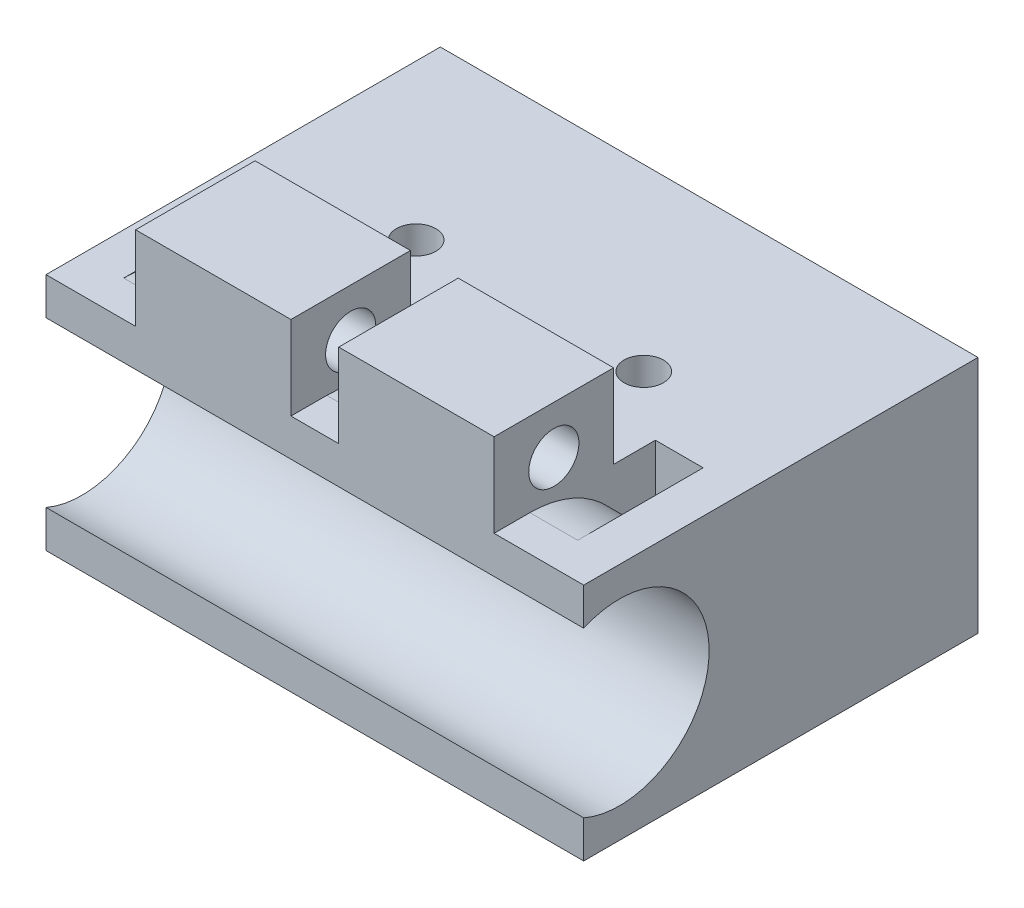
SolidWorks part; units mm, degrees
ref_plane "Front Plane" through (0, 0, 0) normal (0, 0, 1) x (1, 0, 0)
ref_plane "Top Plane" through (0, 0, 0) normal (0, 1, 0) x (1, 0, 0)
ref_plane "Right Plane" through (0, 0, 0) normal (1, 0, 0) x (0, 0, -1)
sketch "Sketch2" plane through (0, 0, 0) normal (0, 0, 1) x (1, 0, 0)
  line L1 (22.5, 10) -> (-22.5, 10)
  line L2 (22.5, 10) -> (22.5, -10)
  line L3 (22.5, -10) -> (-22.5, -10)
  line L4 (-22.5, 10) -> (-22.5, -10)
  line L5 (22.5, 10) -> (-22.5, -10) construction
  line L6 (22.5, -10) -> (-22.5, 10) construction
  point P0 (0, 0)
  dimension "D1" = 20
  dimension "D2" = 45
extrude "Boss-Extrude1" add sketch "Sketch2" along normal blind 33
sketch "Sketch3" plane through (22.5, 0, 0) normal (1, 0, 0) x (0, 0, -1)
  line L0 (-30, 0) -> (0, 0) construction
  circle A0 centre (-30, 0) radius 7.5
  dimension "D1" = 15
  dimension "D2" = 30
extrude "Cut-Extrude1" cut sketch "Sketch3" against normal blind 45
sketch "Sketch4" plane through (0, 0, 0) normal (0, 0, -1) x (-1, 0, 0)
  line L4 (22.5, -10) -> (22.5, 10)
  line L5 (22.5, 10) -> (-22.5, 10)
  line L6 (-22.5, 10) -> (-22.5, -10)
  line L7 (-22.5, -10) -> (22.5, -10)
  line L8 (22.5, -10) -> (22.5, 10)
  line L9 (22.5, 10) -> (-22.5, 10)
  line L10 (-22.5, 10) -> (-22.5, -10)
  line L11 (-22.5, -10) -> (22.5, -10)
  circle A0 centre (-15, 0) radius 4
  circle A1 centre (15, 0) radius 4
  dimension "D2" = 8
  dimension "D3" = 30
  dimension "D4" = 15
  dimension "D1" = 0
extrude "Cut-Extrude2" cut sketch "Sketch4" against normal blind 10 contours A0 | A1 region at (15, 0, 0) region at (-15, 0, 0)
sketch "Sketch5" plane through (0, -10, 0) normal (0, -1, 0) x (1, 0, 0)
  line L0 (0, 19.5) -> (0, 0) construction
  line L1 (-19, 21) -> (-15, 21)
  line L2 (-19, 21) -> (-19, 19.5)
  line L3 (-19, 19.5) -> (-15, 19.5)
  line L4 (-15, 21) -> (-15, 19.5)
  line L5 (-2, 19.5) -> (2, 19.5)
  line L6 (-2, 19.5) -> (-2, 21)
  line L7 (-2, 21) -> (2, 21)
  line L8 (2, 19.5) -> (2, 21)
  line L9 (15, 19.5) -> (19, 19.5)
  line L10 (15, 19.5) -> (15, 21)
  line L11 (15, 21) -> (19, 21)
  line L12 (19, 19.5) -> (19, 21)
  line L13 (-22.5, 19.5) -> (-19, 19.5) construction
  line L14 (-22.5, 33) -> (-22.5, 0) construction
  line L15 (-2, 19.5) -> (-15, 19.5) construction
  line L16 (2, 19.5) -> (15, 19.5) construction
  line L17 (19, 19.5) -> (22.5, 19.5) construction
  line L18 (22.5, 33) -> (22.5, 0) construction
  line L27 (-22.5, 0) -> (22.5, 0) construction
  dimension "D1" = 4
  dimension "D2" = 1.5
  dimension "D3" = 30
  dimension "D4" = 21
extrude "Cut-Extrude3" cut sketch "Sketch5" against normal blind 39
fillet "Fillet1" radius 9 3 edges at (17, -10, 21) (0, -10, 21) (-17, -10, 21)
hole_wizard "M4x0.7 Tapped Hole1" positions "Sketch7" profile "Sketch6" tap size "M4x0.7" standard "ANSI Metric" end condition through all
sketch "Sketch7" plane through (0, -10, 0) normal (0, -1, 0) x (-1, 0, 0)
  line L0 (0, 0) -> (0, -15) construction
  line L3 (9.525, -15) -> (-9.525, -15) construction
  point P0 (-9.525, -15)
  point P2 (9.525, -15)
  dimension "D1" = 19.05
  dimension "D2" = 15
cosmetic thread "Hole Thread1" parameters "D2"=4
cosmetic thread "Hole Thread2" parameters "D2"=4
sketch "Sketch6" plane through (9.525, -10, 15) normal (1, 0, 0) x (0, 0, -1)
  line L0 (0, 0) -> (0, 20)
  line L1 (0, 20) -> (1.65, 20)
  line L2 (1.65, 20) -> (1.65, 0)
  line L5 (1.65, 0) -> (0, 0)
  line L11 (0, -6.35) -> (0, 107.95) construction
  dimension "Thru Tap Drill Dia." = 3.3
  dimension "Thru Tap Drill Depth" = 20
sketch "Sketch8" plane through (0, -10, 0) normal (0, -1, 0) x (1, 0, 0)
  line L0 (-22.5, 33) -> (22.5, 33) construction
  line L1 (-15, 23) -> (-2, 23)
  line L2 (-15, 23) -> (-15, 33)
  line L3 (-15, 33) -> (-2, 33)
  line L4 (-2, 23) -> (-2, 33)
  line L5 (2, 23) -> (15, 23)
  line L6 (2, 23) -> (2, 33)
  line L7 (2, 33) -> (15, 33)
  line L8 (15, 23) -> (15, 33)
  line L9 (-15, 30) -> (-15, 21) construction
  line L13 (15, 21) -> (15, 30) construction
  line L14 (-2, 21) -> (-2, 30) construction
  dimension "D2" = 10
extrude "Boss-Extrude2" add sketch "Sketch8" along normal blind 7
sketch "Sketch14" plane through (-15, 0, 0) normal (-1, 0, 0) x (0, 0, 1)
  line L0 (33, -10) -> (0, -10) construction
  line L1 (28, -13) -> (28, -17) construction
  line L2 (33, -17) -> (23, -17) construction
  circle A0 centre (28, -13) radius 2.1
  dimension "D1" = 4.2
  dimension "D2" = 3
extrude "Cut-Extrude6" cut sketch "Sketch14" against normal through all
move or copy body "Body-Move/Copy1" bodies to move or copy 109 copy no rotation origin (0, -3.5, 0) rotation axis (0, 0, 1) rotation angle 180
